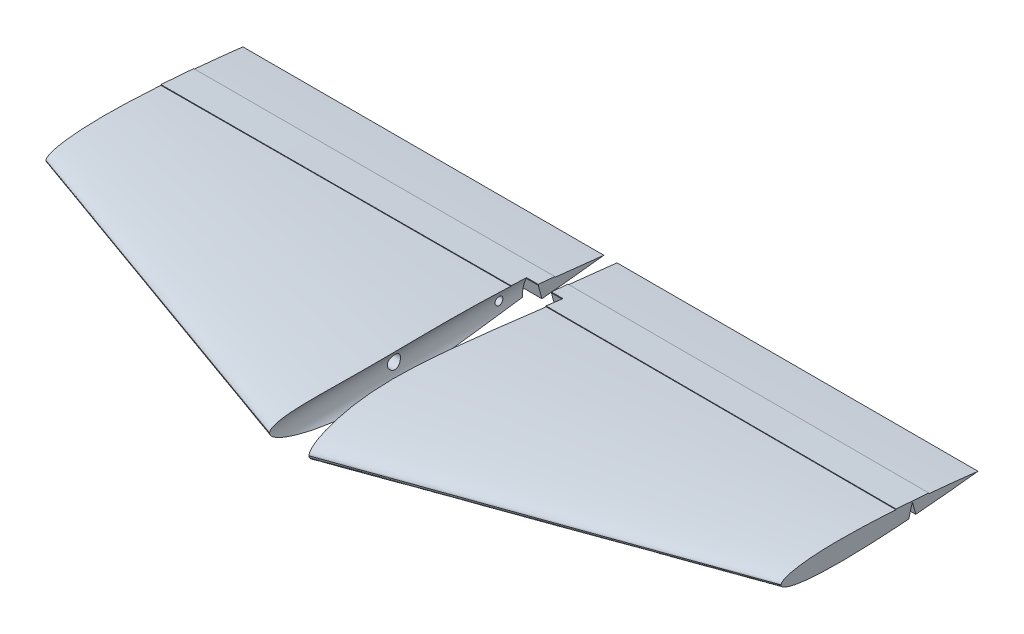
SolidWorks part; units mm, degrees
ref_plane "Front Plane" through (0, 0, 0) normal (0, 0, 1) x (1, 0, 0)
ref_plane "Top Plane" through (0, 0, 0) normal (0, 1, 0) x (1, 0, 0)
ref_plane "Right Plane" through (0, 0, 0) normal (1, 0, 0) x (0, 0, -1)
sketch "Sketch3" plane through (0, 0, 0) normal (1, 0, 0) x (0, 0, -1)
  line L0 (0, 0) -> (-250, 0) construction
  spline S0 degree 4 poles (-250, 0) (-249.9999, 0.1958) (-249.9612, 0.6039) (-249.7596, 1.2633) (-249.1282, 2.2398) (-248.1098, 3.1752) (-246.5761, 4.1828) (-244.1271, 5.3667) (-240.0739, 6.8179) (-232.84, 8.6113) (-221.2945, 10.4497) (-205.8077, 11.8178) (-187.4923, 12.5325) (-167.6157, 12.5624) (-147.9613, 12.1042) (-127.9831, 11.2209) (-108.5655, 10.1073) (-88.2725, 8.6479) (-69.4578, 7.1641) (-48.2492, 5.205) (-31.0441, 3.5474) (-5.6278, 0.7144) (5.3818, -0.6305) (19.3913, -2.4508) (24.9342, -3.2323) knots 0 0 0 0 0 0.002791 0.005883 0.009735 0.016522 0.022438 0.032158 0.048634 0.078249 0.129037 0.199997 0.270957 0.341918 0.412878 0.483838 0.554798 0.625759 0.696719 0.767679 0.83864 0.9096 1 1 1 1 1 construction
  spline S1 degree 4 poles (-250, 0) (-249.9999, 0.1958) (-249.9612, 0.6039) (-249.7596, 1.2633) (-249.1282, 2.2398) (-248.1098, 3.1752) (-246.5761, 4.1828) (-244.1271, 5.3667) (-240.0739, 6.8179) (-232.84, 8.6113) (-221.2945, 10.4497) (-205.8077, 11.8178) (-187.4923, 12.5325) (-167.6157, 12.5624) (-147.9613, 12.1042) (-127.9831, 11.2209) (-108.5655, 10.1073) (-88.2725, 8.6479) (-69.4578, 7.1641) (-48.2492, 5.205) (-31.0441, 3.5474) (-13.2038, 1.5588) (-4.4672, 0.5411) (0, 0) knots 0 0 0 0 0 0.002791 0.005883 0.009735 0.016522 0.022438 0.032158 0.048634 0.078249 0.129037 0.199997 0.270957 0.341918 0.412878 0.483838 0.554798 0.625759 0.696719 0.767679 0.83864 0.9096 0.9096 0.9096 0.9096 0.9096
  spline S2 degree 4 poles (-250, 0) (-249.9999, -0.1958) (-249.9612, -0.6039) (-249.7596, -1.2633) (-249.1282, -2.2398) (-248.1098, -3.1752) (-246.5761, -4.1828) (-244.1271, -5.3667) (-240.0739, -6.8179) (-232.84, -8.6113) (-221.2945, -10.4497) (-205.8077, -11.8178) (-187.4923, -12.5325) (-167.6157, -12.5624) (-147.9613, -12.1042) (-127.9831, -11.2209) (-108.5655, -10.1073) (-88.2725, -8.6479) (-69.4578, -7.1641) (-48.2492, -5.205) (-31.0441, -3.5474) (-13.2038, -1.5588) (-4.4672, -0.5411) (0, 0) knots 0 0 0 0 0 0.002791 0.005883 0.009735 0.016522 0.022438 0.032158 0.048634 0.078249 0.129037 0.199997 0.270957 0.341918 0.412878 0.483838 0.554798 0.625759 0.696719 0.767679 0.83864 0.9096 0.9096 0.9096 0.9096 0.9096
  dimension "D1" = 250
ref_plane "Plane1" through (280, 0, 0) normal (1, 0, 0) x (0, 0, -1)
sketch "Sketch4" plane through (280, 0, 0) normal (1, 0, 0) x (0, 0, -1)
  line L0 (0, 0) -> (-150, 0) construction
  spline S0 degree 4 poles (-150, 0) (-149.9999, 0.1175) (-149.9767, 0.3624) (-149.8557, 0.758) (-149.4769, 1.3439) (-148.8659, 1.9051) (-147.9457, 2.5097) (-146.4763, 3.22) (-144.0443, 4.0908) (-139.704, 5.1668) (-132.7767, 6.2698) (-123.4846, 7.0907) (-112.4954, 7.5195) (-100.5694, 7.5374) (-88.7768, 7.2625) (-76.7899, 6.7325) (-65.1393, 6.0644) (-52.9635, 5.1887) (-41.6747, 4.2985) (-28.9495, 3.123) (-18.6265, 2.1284) (-3.3767, 0.4286) (3.2291, -0.3783) (11.6348, -1.4705) (14.9605, -1.9394) knots 0 0 0 0 0 0.002791 0.005883 0.009735 0.016522 0.022438 0.032158 0.048634 0.078249 0.129037 0.199997 0.270957 0.341918 0.412878 0.483838 0.554798 0.625759 0.696719 0.767679 0.83864 0.9096 1 1 1 1 1 construction
  spline S1 degree 4 poles (-150, 0) (-149.9999, 0.1175) (-149.9767, 0.3624) (-149.8557, 0.758) (-149.4769, 1.3439) (-148.8659, 1.9051) (-147.9457, 2.5097) (-146.4763, 3.22) (-144.0443, 4.0908) (-139.704, 5.1668) (-132.7767, 6.2698) (-123.4846, 7.0907) (-112.4954, 7.5195) (-100.5694, 7.5374) (-88.7768, 7.2625) (-76.7899, 6.7325) (-65.1393, 6.0644) (-52.9635, 5.1887) (-41.6747, 4.2985) (-28.9495, 3.123) (-18.6265, 2.1284) (-7.9223, 0.9353) (-2.6803, 0.3247) (0, 0) knots 0 0 0 0 0 0.002791 0.005883 0.009735 0.016522 0.022438 0.032158 0.048634 0.078249 0.129037 0.199997 0.270957 0.341918 0.412878 0.483838 0.554798 0.625759 0.696719 0.767679 0.83864 0.9096 0.9096 0.9096 0.9096 0.9096
  spline S2 degree 4 poles (-150, 0) (-149.9999, -0.1175) (-149.9767, -0.3624) (-149.8557, -0.758) (-149.4769, -1.3439) (-148.8659, -1.9051) (-147.9457, -2.5097) (-146.4763, -3.22) (-144.0443, -4.0908) (-139.704, -5.1668) (-132.7767, -6.2698) (-123.4846, -7.0907) (-112.4954, -7.5195) (-100.5694, -7.5374) (-88.7768, -7.2625) (-76.7899, -6.7325) (-65.1393, -6.0644) (-52.9635, -5.1887) (-41.6747, -4.2985) (-28.9495, -3.123) (-18.6265, -2.1284) (-7.9223, -0.9353) (-2.6803, -0.3247) (0, 0) knots 0 0 0 0 0 0.002791 0.005883 0.009735 0.016522 0.022438 0.032158 0.048634 0.078249 0.129037 0.199997 0.270957 0.341918 0.412878 0.483838 0.554798 0.625759 0.696719 0.767679 0.83864 0.9096 0.9096 0.9096 0.9096 0.9096
loft "Loft1" add profiles "Sketch3", "Sketch4" connector at (0, 0, 0) connector at (280, 0, 0)
sketch "Sketch6" plane through (0, 0, 0) normal (-1, 0, 0) x (0, 0, 1)
  line L0 (0, 0) -> (249.9998, 0) construction
  line L1 (50, 0) -> (50, 5.2226) construction
  line L2 (50, 5.2226) -> (52.9065, -5.6245)
  line L3 (50, 5.2226) -> (47.2363, -5.0918)
  line L4 (52.9065, -5.6245) -> (53.3084, -7.1245)
  line L5 (53.3084, -7.1245) -> (46.6916, -7.1245)
  line L6 (46.6916, -7.1245) -> (47.2363, -5.0918)
  spline S1 degree 3 poles (249.9998, 0) (249.9998, -0.3303) (249.8759, -0.9899) (249.3864, -1.8624) (248.7238, -2.6034) (247.962, -3.2402) (247.1416, -3.797) (246.2828, -4.2923) (245.3979, -4.7388) (244.193, -5.2813) (242.6531, -5.88) (240.7719, -6.5042) (238.8684, -7.0564) (236.9492, -7.551) (235.0183, -7.9974) (233.0787, -8.4038) (231.1322, -8.7761) (229.1802, -9.1183) (227.2237, -9.4331) (225.2633, -9.7232) (223.2997, -9.9908) (220.6781, -10.3206) (217.3955, -10.6866) (213.4499, -11.0625) (209.4994, -11.3825) (205.5452, -11.6532) (201.5883, -11.8796) (197.6292, -12.0662) (193.6687, -12.2161) (188.3864, -12.3703) (181.7816, -12.4844) (173.8547, -12.5144) (165.9281, -12.4534) (158.0025, -12.3124) (150.0786, -12.0979) (142.1568, -11.8164) (134.2373, -11.4769) (126.32, -11.0887) (118.4051, -10.6559) (110.4927, -10.178) (102.5832, -9.6561) (94.6761, -9.0972) (86.7712, -8.5097) (78.8683, -7.8944) (70.9683, -7.2438) (63.0715, -6.5557) (55.1773, -5.8381) (47.285, -5.1002) (39.3948, -4.3397) (31.5085, -3.54) (23.6262, -2.7007) (13.1211, -1.5408) (5.2462, -0.6354) (0, 0) knots 0.499997 0.499997 0.499997 0.499997 0.50195 0.503903 0.505856 0.507809 0.509763 0.511716 0.513669 0.515622 0.519528 0.523435 0.527341 0.531247 0.535153 0.53906 0.542966 0.546872 0.550778 0.554685 0.558591 0.562497 0.57031 0.578122 0.585935 0.593748 0.60156 0.609373 0.617185 0.624998 0.640623 0.656248 0.671873 0.687498 0.703123 0.718748 0.734373 0.749998 0.765624 0.781249 0.796874 0.812499 0.828124 0.843749 0.859374 0.874999 0.890624 0.906249 0.921875 0.9375 0.953125 0.96875 1 1 1 1 construction
  dimension "D1" = 50
  dimension "D2" = 15
  dimension "D3" = 15
  dimension "D4" = 1.5
sketch "Sketch7" plane through (280, 0, 0) normal (1, 0, 0) x (0, 0, -1)
  line L0 (-149.9999, 0) -> (0, 0) construction
  line L1 (-50, 0) -> (-50, 4.8685) construction
  line L2 (-50, 4.8685) -> (-47.425, -4.7416)
  line L3 (-50, 4.8685) -> (-52.6846, -5.1507)
  line L4 (-52.6846, -5.1507) -> (-53.0866, -6.6507)
  line L5 (-53.0866, -6.6507) -> (-46.9134, -6.6507)
  line L6 (-46.9134, -6.6507) -> (-47.425, -4.7416)
  spline S1 degree 2 poles (-149.9999, 0) (-149.9999, -1.0092) (-148.7713, -1.9362) (-147.9824, -2.5314) (-146.6951, -3.0843) (-144.8841, -3.862) (-142.1683, -4.5258) (-138.2655, -5.4797) (-132.7998, -6.141) (-128.4814, -6.6636) (-123.3268, -6.9875) (-118.8418, -7.2693) (-113.824, -7.3959) (-105.2058, -7.6134) (-94.8016, -7.3801) (-86.1557, -7.1862) (-75.7922, -6.6487) (-71.0007, -6.4001) (-66.2959, -6.1026) (-61.9956, -5.8307) (-56.8059, -5.4552) (-51.7767, -5.0913) (-47.3212, -4.7333) (-42.7854, -4.3688) (-37.8431, -3.9303) (-33.2978, -3.527) (-28.3712, -3.0577) (-23.1272, -2.5583) (-18.9054, -2.1204) (-14.7262, -1.687) (-9.4487, -1.0957) (-4.0863, -0.4949) (0, 0) knots 0 0 0 0.015625 0.015625 0.03125 0.03125 0.0625 0.0625 0.125 0.125 0.1875 0.1875 0.25 0.25 0.375 0.375 0.5 0.5 0.5625 0.5625 0.625 0.625 0.6875 0.6875 0.75 0.75 0.8125 0.8125 0.875 0.875 0.9375 0.9375 1 1 1 construction
  dimension "D1" = 50
  dimension "D2" = 15
  dimension "D3" = 15
  dimension "D4" = 1.5
loft "Cut-Loft1" cut profiles "Sketch6", "Sketch7" connector at (0, -5.0918, 47.2363) connector at (280, -4.7416, 47.425)
sketch "Sketch8" plane through (0, 0, 0) normal (-1, 0, 0) x (0, 0, 1)
  line L0 (0, 0) -> (249.9998, 0) construction
  circle A0 centre (70, 0) radius 3
  point P4 (70, 0)
  dimension "D1" = 70
  dimension "D2" = 6
sketch "Sketch15" plane through (280, 0, 0) normal (1, 0, 0) x (0, 0, -1)
  line L0 (-62.5, 5.8541) -> (-37.5, 3.8998)
  line L1 (-37.5, 3.8998) -> (-37.4609, 4.3998)
  line L2 (-37.4609, 4.3998) -> (-62.4609, 6.3541)
  line L3 (-62.4609, 6.3541) -> (-62.5, 5.8541)
  spline S0 degree 2 poles (0, 0) (-4.0859, 0.4949) (-9.4487, 1.0957) (-14.7252, 1.6868) (-18.9054, 2.1204) (-23.1261, 2.5582) (-28.3712, 3.0577) (-33.2967, 3.5269) (-37.8431, 3.9303) (-42.7843, 4.3687) (-47.3212, 4.7333) (-51.7756, 5.0912) (-56.8059, 5.4552) (-61.9946, 5.8306) (-66.2959, 6.1026) (-70.9996, 6.4001) (-75.7922, 6.6487) (-86.1547, 7.1862) (-94.8016, 7.3801) (-105.2047, 7.6134) (-113.824, 7.3959) (-118.8407, 7.2694) (-123.3268, 6.9875) (-128.4803, 6.6637) (-132.7998, 6.141) (-138.2644, 5.4798) (-142.1683, 4.5258) (-144.883, 3.8624) (-146.6951, 3.0843) (-147.9815, 2.5319) (-148.7713, 1.9362) (-149.9999, 1.0095) (-149.9999, 0) knots 0 0 0 0.0625 0.0625 0.125 0.125 0.1875 0.1875 0.25 0.25 0.3125 0.3125 0.375 0.375 0.4375 0.4375 0.5 0.5 0.625 0.625 0.75 0.75 0.8125 0.8125 0.875 0.875 0.9375 0.9375 0.96875 0.96875 0.984375 0.984375 1 1 1 construction
  dimension "D1" = 0.5
  dimension "D2" = 25
  dimension "D3" = 12.5
sketch "Sketch16" plane through (0, 0, 0) normal (-1, 0, 0) x (0, 0, 1)
  line L0 (37.4356, 4.1381) -> (62.4356, 6.494)
  line L1 (37.4356, 4.1381) -> (37.3884, 4.6381)
  line L2 (62.4356, 6.494) -> (62.3884, 6.994)
  line L3 (37.3884, 4.6381) -> (62.3884, 6.994)
  spline S0 degree 3 poles (0, 0) (5.2462, 0.6354) (13.1211, 1.5408) (23.6262, 2.7007) (31.5085, 3.54) (39.3948, 4.3397) (47.285, 5.1002) (55.1773, 5.8381) (63.0715, 6.5557) (70.9683, 7.2438) (78.8683, 7.8944) (86.7712, 8.5097) (94.6761, 9.0972) (102.5832, 9.6561) (110.4927, 10.178) (118.4051, 10.6559) (126.32, 11.0887) (134.2373, 11.4769) (142.1568, 11.8164) (150.0786, 12.0979) (158.0025, 12.3124) (165.9281, 12.4534) (173.8547, 12.5144) (181.7816, 12.4844) (188.3864, 12.3703) (193.6687, 12.2161) (197.6292, 12.0662) (201.5883, 11.8796) (205.5452, 11.6532) (209.4994, 11.3825) (213.4499, 11.0625) (217.3955, 10.6866) (220.6781, 10.3206) (223.2997, 9.9908) (225.2633, 9.7232) (227.2237, 9.4331) (229.1802, 9.1183) (231.1322, 8.7761) (233.0787, 8.4038) (235.0183, 7.9974) (236.9492, 7.551) (238.8684, 7.0564) (240.7719, 6.5042) (242.6531, 5.88) (244.193, 5.2813) (245.3979, 4.7388) (246.2828, 4.2923) (247.1416, 3.797) (247.962, 3.2402) (248.7238, 2.6034) (249.3864, 1.8624) (249.8759, 0.9899) (249.9998, 0.3303) (249.9998, 0) knots 0 0 0 0 0.03125 0.046875 0.0625 0.078125 0.093749 0.109374 0.124999 0.140624 0.156249 0.171874 0.187499 0.203124 0.218749 0.234374 0.249998 0.265623 0.281248 0.296873 0.312498 0.328123 0.343748 0.359373 0.374998 0.38281 0.390623 0.398435 0.406248 0.41406 0.421872 0.429685 0.437497 0.441404 0.44531 0.449216 0.453122 0.457028 0.460935 0.464841 0.468747 0.472653 0.47656 0.480466 0.484372 0.486325 0.488278 0.490231 0.492184 0.494138 0.496091 0.498044 0.499997 0.499997 0.499997 0.499997 construction
  dimension "D1" = 0.5
  dimension "D2" = 25
  dimension "D3" = 12.5
loft "Loft2" add profiles "Sketch15", "Sketch16" connector at (280, 4.3998, 37.4609) connector at (0, 4.6381, 37.3884)
ref_plane "Plane4" through (0, 0, 50) normal (0, 0, 1) x (1, 0, 0)
sketch "Sketch17" plane through (0, 0, 0) normal (0, 1, 0) x (1, 0, 0)
  line L0 (0, -14.3) -> (0, 14.3) construction
  line L1 (40, -80) -> (84, -80)
  line L2 (40, -80) -> (40, -124)
  line L3 (40, -124) -> (84, -124)
  line L4 (84, -80) -> (84, -124)
  line L5 (-40, -80) -> (-84, -80)
  line L6 (-40, -80) -> (-40, -124)
  line L7 (-40, -124) -> (-84, -124)
  line L8 (-84, -80) -> (-84, -124)
  line L9 (-14.3, 0) -> (14.3, 0) construction
  dimension "D1" = 44
  dimension "D2" = 44
  dimension "D3" = 44
  dimension "D4" = 44
  dimension "D5" = 40
  dimension "D6" = 80
  dimension "D7" = 80
  dimension "D8" = 40
extrude "Cut-Extrude7" cut sketch "Sketch17" against normal through all and the other way blind 5
extrude "Cut-Extrude10" cut sketch "Sketch8" against normal blind 100
sketch "Sketch18" plane through (0, 0, 0) normal (1, 0, 0) x (0, 0, -1)
  line L0 (0, 0) -> (-250, 0) construction
  circle A0 centre (-150, 0) radius 5
  dimension "D2" = 10
  dimension "D1" = 250
  dimension "D3" = 100
extrude "Cut-Extrude11" cut sketch "Sketch18" along normal blind 150 contours A0
sketch "Sketch19" plane through (0, 0, 0) normal (1, 0, 0) x (0, 0, -1)
  circle A0 centre (-70, 0) radius 4
  circle A1 centre (-150, 0) radius 4
  circle A2 centre (-150, 0) radius 5
  circle A3 centre (-70, 0) radius 4.95
  dimension "D1" = 9.9
  dimension "D2" = 10
  dimension "D3" = 8
  dimension "D4" = 8
mirror "Mirror7" about plane through (0, 0, 0) normal (1, 0, 0) of "Cut-Extrude7", "Cut-Extrude11", "Cut-Extrude10", "Cut-Loft1", "Loft2", "Loft1"
sketch "Sketch13" plane through (0, 0, 50) normal (0, 0, 1) x (1, 0, 0)
  circle A0 centre (0, 0) radius 15
  dimension "D1" = 30
extrude "Cut-Extrude5" cut sketch "Sketch13" along normal through all
sketch "Sketch14" plane through (0, 0, 0) normal (0, 1, 0) x (1, 0, 0)
  line L0 (0, -14.3) -> (0, 14.3) construction
  line L1 (-5, 0) -> (5, 0)
  line L2 (-5, 0) -> (-5, -75)
  line L3 (-5, -75) -> (5, -75)
  line L4 (5, 0) -> (5, -75)
  line L5 (-14.3, 0) -> (14.3, 0) construction
  dimension "10" = 10
  dimension "D2" = 5
  dimension "D3" = 75
extrude "Cut-Extrude6" cut sketch "Sketch14" against normal through all and the other way through all
